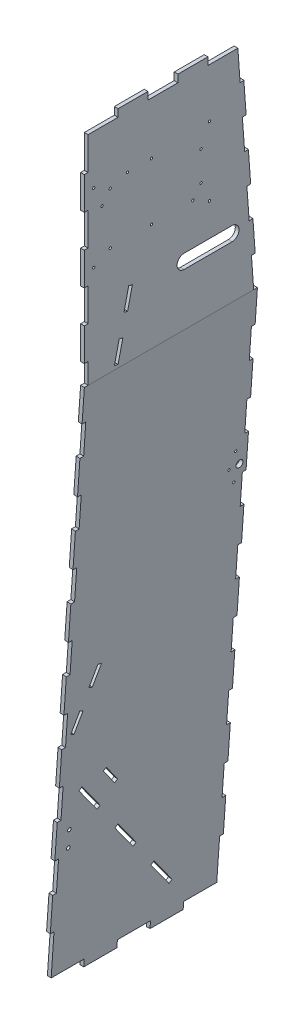
SolidWorks part; units mm, degrees
material "A-Glass Fiber"
ref_plane "Front Plane" through (0, 0, 0) normal (0, 0, 1) x (1, 0, 0)
ref_plane "Top Plane" through (0, 0, 0) normal (0, 1, 0) x (1, 0, 0)
ref_plane "Right Plane" through (0, 0, 0) normal (1, 0, 0) x (0, 0, -1)
sketch "Sketch1" plane through (0, 0, 0) normal (0, 0, 1) x (1, 0, 0)
  line L0 (-215.8818, 2052.32) -> (-215.8818, 1463.04)
  line L1 (-215.8818, 1463.04) -> (-316.0886, 20.32)
  line L2 (-316.0886, 20.32) -> (-317.5, 0)
  line L4 (-215.8818, 2052.32) -> (-215.8818, 2072.64)
  line L6 (-215.8818, 2072.64) -> (-205.7153, 2072.64)
  line L7 (-205.7153, 2072.64) -> (-205.7153, 1463.04)
  line L8 (-205.7153, 1463.04) -> (-307.3335, 0)
  line L9 (-317.5, 0) -> (-307.3335, 0)
  line L10 (-371.5407, 0) -> (-280.9748, 0) construction
  line L13 (-371.5407, 20.32) -> (-280.9748, 20.32) construction
  line L15 (-205.7153, 1463.04) -> (205.7153, 1463.04) construction
  point P23 (-305.9221, 20.32)
  dimension "D1" = 307.3335
extrude "Boss-Extrude1" add sketch "Sketch1" against normal blind 469.9
sketch "Sketch2" plane through (-315.9757, 21.9467, 0) normal (-0.9976, 0.0693, 0) x (0, 0, 1)
  line L35 (0, 1355.6785) -> (0, 0.1049)
  line L37 (-234.95, 1444.5652) -> (-234.95, -21.9996) construction
  line L40 (-10.16, 0.1049) -> (0, 0.1049)
  line L43 (-10.16, 0.1049) -> (-10.16, -21.9996)
  line L46 (0, 1272.0274) -> (-10.16, 1272.0274)
  line L47 (-10.16, 1355.6785) -> (-10.16, 1272.0274)
  line L48 (0, 1355.6785) -> (-10.16, 1355.6785)
  line L49 (0, 1177.9051) -> (-10.16, 1177.9051)
  line L50 (-10.16, 1177.9051) -> (-10.16, 1094.2274)
  line L51 (0, 1094.2274) -> (-10.16, 1094.2274)
  line L52 (0, 916.4274) -> (-10.16, 916.4274)
  line L53 (-10.16, 1000.1317) -> (-10.16, 916.4274)
  line L54 (0, 1000.1317) -> (-10.16, 1000.1317)
  line L55 (0, 822.3583) -> (-10.16, 822.3583)
  line L56 (0, 738.6274) -> (-10.16, 738.6274)
  line L57 (-10.16, 822.3583) -> (-10.16, 738.6274)
  line L58 (0, 644.5849) -> (-10.16, 644.5849)
  line L59 (-10.16, 644.5849) -> (-10.16, 560.8274)
  line L60 (0, 560.8274) -> (-10.16, 560.8274)
  line L61 (0, 466.8115) -> (-10.16, 466.8115)
  line L62 (-10.16, 466.8115) -> (-10.16, 383.0274)
  line L63 (0, 383.0274) -> (-10.16, 383.0274)
  line L64 (0, 289.0381) -> (-10.16, 289.0381)
  line L65 (-10.16, 289.0381) -> (-10.16, 205.2274)
  line L66 (0, 205.2274) -> (-10.16, 205.2274)
  line L67 (0, 111.2647) -> (-10.16, 111.2647)
  line L68 (-10.16, 111.2647) -> (-10.16, 0.1049)
  line L69 (0, 0.1049) -> (-10.16, 0.1049)
  line L70 (-10.16, -21.9996) -> (0, -21.9996)
  line L71 (0, 0.1049) -> (0, -21.9996)
  line L72 (-469.9, 1444.5652) -> (0, 1444.5652) construction
  line L73 (-469.9, -21.9996) -> (0, -21.9996) construction
  line L74 (-469.9, 0.1049) -> (-469.9, -21.9996)
  line L75 (-459.74, -21.9996) -> (-469.9, -21.9996)
  line L76 (-469.9, 0.1049) -> (-459.74, 0.1049)
  line L77 (-459.74, 111.2647) -> (-459.74, 0.1049)
  line L78 (-469.9, 111.2647) -> (-459.74, 111.2647)
  line L79 (-469.9, 205.2274) -> (-459.74, 205.2274)
  line L80 (-459.74, 289.0381) -> (-459.74, 205.2274)
  line L81 (-469.9, 289.0381) -> (-459.74, 289.0381)
  line L82 (-469.9, 383.0274) -> (-459.74, 383.0274)
  line L83 (-459.74, 466.8115) -> (-459.74, 383.0274)
  line L84 (-469.9, 466.8115) -> (-459.74, 466.8115)
  line L85 (-469.9, 560.8274) -> (-459.74, 560.8274)
  line L86 (-459.74, 644.5849) -> (-459.74, 560.8274)
  line L87 (-469.9, 644.5849) -> (-459.74, 644.5849)
  line L88 (-459.74, 822.3583) -> (-459.74, 738.6274)
  line L89 (-469.9, 738.6274) -> (-459.74, 738.6274)
  line L90 (-469.9, 822.3583) -> (-459.74, 822.3583)
  line L91 (-469.9, 1000.1317) -> (-459.74, 1000.1317)
  line L92 (-459.74, 1000.1317) -> (-459.74, 916.4274)
  line L93 (-469.9, 916.4274) -> (-459.74, 916.4274)
  line L94 (-469.9, 1094.2274) -> (-459.74, 1094.2274)
  line L95 (-459.74, 1177.9051) -> (-459.74, 1094.2274)
  line L96 (-469.9, 1177.9051) -> (-459.74, 1177.9051)
  line L97 (-469.9, 1355.6785) -> (-459.74, 1355.6785)
  line L98 (-459.74, 1355.6785) -> (-459.74, 1272.0274)
  line L99 (-469.9, 1272.0274) -> (-459.74, 1272.0274)
  line L100 (-459.74, 0.1049) -> (-459.74, -21.9996)
  line L101 (-459.74, 0.1049) -> (-469.9, 0.1049)
  line L102 (-469.9, 1355.6785) -> (-469.9, 0.1049)
  line L103 (-469.9, 1444.5652) -> (-469.9, -21.9996) construction
  line L104 (-459.74, 205.2274) -> (-469.9, 205.2274) construction
  line M1 (0, -21.9996) -> (0, 1444.5652)
  line M3 (-469.9, 1444.5652) -> (-469.9, -21.9996)
  line M4 (-469.9, -21.9996) -> (0, -21.9996)
extrude "Cut-Extrude1" cut sketch "Sketch2" against normal blind 10.16 contours L66 L35 L64 L65 | L69 L67 L68 M1 | L60 L35 L58 L59 | L63 L35 L61 L62 | L55 L57 L56 L35 | L35 L54 L53 L52 | L51 L35 L49 L50 | L35 L48 L47 L46 | L40 L43 M4 M1 | L100 L76 M3 M4 | L78 L76 L77 M3 | L81 L79 L80 M3 | L84 L82 L83 M3 | L87 L85 L86 M3 | L90 L89 L88 M3 | L93 L92 L91 M3 | L96 L94 L95 M3 | L99 L98 L97 M3 region at (-224.9388, 1332.6419, -464.82) region at (-237.2577, 1155.2825, -464.82) region at (-249.5765, 977.9231, -464.82) region at (-261.8953, 800.5637, -464.82) region at (-274.2142, 623.2043, -464.82) region at (-286.533, 445.8449, -464.82) region at (-298.8518, 268.4855, -464.82) region at (-316.7342, 11.0257, -464.82) region at (-312.1173, 77.4977, -5.08) region at (-298.8518, 268.4855, -5.08) region at (-286.533, 445.8449, -5.08) region at (-274.2142, 623.2043, -5.08) region at (-261.8953, 800.5637, -5.08) region at (-249.5765, 977.9231, -5.08) region at (-237.2577, 1155.2825, -5.08) region at (-224.9388, 1332.6419, -5.08) region at (-316.7342, 11.0257, -5.08) region at (-312.1173, 77.4977, -464.82)
sketch "Sketch3" plane through (-215.8818, 0, 0) normal (-1, 0, 0) x (0, 0, 1)
  line L0 (0, 2052.32) -> (-10.16, 2052.32) construction
  line L1 (0, 1963.42) -> (-10.16, 1963.42) construction
  line L2 (-10.16, 2052.32) -> (-10.16, 1963.42) construction
  line L3 (0, 1874.52) -> (-10.16, 1874.52) construction
  line L4 (0, 1463.04) -> (0, 2072.64)
  line L5 (0, 2072.64) -> (-469.9, 2072.64)
  line L6 (-469.9, 2072.64) -> (-469.9, 1463.04)
  line L8 (0, 1463.04) -> (0, 2072.64)
  line L9 (0, 2072.64) -> (-469.9, 2072.64)
  line L12 (0, 1785.62) -> (-10.16, 1785.62) construction
  line L13 (-10.16, 1874.52) -> (-10.16, 1785.62) construction
  line L14 (0, 1696.72) -> (-10.16, 1696.72) construction
  line L15 (0, 1607.82) -> (-10.16, 1607.82) construction
  line L16 (-10.16, 1696.72) -> (-10.16, 1607.82) construction
  line L17 (0, 1518.92) -> (-10.16, 1518.92) construction
  line L18 (-10.16, 1518.92) -> (-10.16, 1488.44) construction
  line L19 (0, 2052.32) -> (-10.16, 2052.32)
  line L20 (0, 1963.42) -> (-10.16, 1963.42)
  line L21 (-10.16, 2052.32) -> (-10.16, 1963.42)
  line L22 (0, 1874.52) -> (-10.16, 1874.52)
  line L23 (0, 1785.62) -> (-10.16, 1785.62)
  line L24 (-10.16, 1874.52) -> (-10.16, 1785.62)
  line L25 (0, 1696.72) -> (-10.16, 1696.72)
  line L26 (0, 1607.82) -> (-10.16, 1607.82)
  line L27 (-10.16, 1696.72) -> (-10.16, 1607.82)
  line L28 (0, 1518.92) -> (-10.16, 1518.92)
  line L29 (-10.16, 1518.92) -> (-10.16, 1488.44)
  line L30 (0, 2052.32) -> (0, 1463.04)
  line L31 (-234.95, 1463.04) -> (-234.95, 2072.64) construction
  line L32 (-10.16, 2052.32) -> (0, 2052.32)
  line L33 (-10.16, 2052.32) -> (-10.16, 2072.64)
  line L34 (-10.16, 2072.64) -> (0, 2072.64)
  line L35 (0, 2052.32) -> (0, 2072.64)
  line L36 (-469.9, 1463.04) -> (-425.45, 2072.64)
  line L37 (-469.9, 1463.04) -> (-463.754, 1547.3284)
  line L38 (-469.9, 1463.04) -> (-459.7669, 1462.3011)
  line L39 (-463.754, 1547.3284) -> (-453.6209, 1546.5895)
  line L40 (-459.7669, 1462.3011) -> (-453.6209, 1546.5895)
  line L41 (-463.754, 1547.3284) -> (-453.6209, 1546.5895)
  line L42 (-463.754, 1547.3284) -> (-457.6079, 1631.6168)
  line L43 (-453.6209, 1546.5895) -> (-447.4748, 1630.8779)
  line L44 (-457.6079, 1631.6168) -> (-447.4748, 1630.8779)
  line L45 (-457.6079, 1631.6168) -> (-447.4748, 1630.8779)
  line L46 (-457.6079, 1631.6168) -> (-451.4619, 1715.9052)
  line L47 (-447.4748, 1630.8779) -> (-441.3288, 1715.1664)
  line L48 (-451.4619, 1715.9052) -> (-441.3288, 1715.1664)
  line L49 (-451.4619, 1715.9052) -> (-441.3288, 1715.1664)
  line L50 (-451.4619, 1715.9052) -> (-445.3159, 1800.1936)
  line L51 (-441.3288, 1715.1664) -> (-435.1828, 1799.4548)
  line L52 (-445.3159, 1800.1936) -> (-435.1828, 1799.4548)
  line L53 (-445.3159, 1800.1936) -> (-435.1828, 1799.4548)
  line L54 (-10.16, 1488.44) -> (-10.16, 1463.04)
  line L56 (-445.3159, 1800.1936) -> (-439.1699, 1884.4821)
  line L57 (-435.1828, 1799.4548) -> (-429.0368, 1883.7432)
  line L58 (-439.1699, 1884.4821) -> (-429.0368, 1883.7432)
  line L59 (-439.1699, 1884.4821) -> (-429.0368, 1883.7432)
  line L60 (-439.1699, 1884.4821) -> (-433.0238, 1968.7705)
  line L61 (-429.0368, 1883.7432) -> (-422.8907, 1968.0316)
  line L62 (-433.0238, 1968.7705) -> (-422.8907, 1968.0316)
  line L63 (-10.16, 2052.32) -> (-469.9, 2052.32) construction
  line L64 (-469.9, 2072.64) -> (-469.9, 1463.04) construction
  line L65 (-433.0238, 1968.7705) -> (-422.8907, 1968.0316)
  line L66 (-433.0238, 1968.7705) -> (-426.8778, 2053.0589)
  line L67 (-422.8907, 1968.0316) -> (-416.7447, 2052.32)
  line L68 (-426.8778, 2053.0589) -> (-416.7447, 2052.32)
  line L69 (-416.7447, 2052.32) -> (-426.9317, 2052.32)
  line L70 (-426.8778, 2053.0589) -> (-416.7447, 2052.32)
  line L71 (-426.8778, 2053.0589) -> (-425.3531, 2073.9694)
  line L72 (-416.7447, 2052.32) -> (-415.22, 2073.2306)
  line L73 (-425.3531, 2073.9694) -> (-415.22, 2073.2306)
  line L74 (-469.9, 1463.04) -> (0, 1463.04) construction
  line L78 (-469.9, 1463.04) -> (0, 1463.04)
  line L79 (-469.9, 1463.04) -> (0, 1463.04)
  line M7 (0, 1463.04) -> (0, 2072.64)
  line M8 (0, 2072.64) -> (-469.9, 2072.64)
  line M9 (-469.9, 2072.64) -> (-469.9, 1463.04)
  line M10 (-469.9, 1463.04) -> (0, 1463.04)
  dimension "D2" = 44.45
  dimension "D3" = 10.16
  dimension "D1" = 0
extrude "Cut-Extrude2" cut sketch "Sketch3" against normal blind 12.7 contours M10 | L29 L54 L28 M10 M7 | L36 L66 M9 M8 | L48 L36 L44 L47 | L58 L36 L52 L57 | L67 L69 L36 L62 | L25 L27 L26 L8 | L22 L24 L23 L8 | L19 L21 L20 L8 | L33 L19 L8 M8 | L68 L72 L36 M8 | L69 L68 L66 region at (-215.8818, 1490.98, -5.08) region at (-215.8818, 1652.27, -5.08) region at (-215.8818, 1504.9998, -461.7544) region at (-215.8818, 1869.44, -455.0833) region at (-215.8818, 1830.07, -5.08) region at (-215.8818, 1673.3916, -449.4684) region at (-215.8818, 2062.6636, -421.0525) region at (-215.8818, 2007.87, -5.08) region at (-215.8818, 1841.9684, -437.1763) region at (-215.8818, 2052.5663, -423.5181) region at (-215.8818, 2062.48, -5.08) region at (-215.8818, 2010.3602, -424.8903)
sketch "Sketch4" plane through (-215.8818, 0, 0) normal (-1, 0, 0) x (0, 0, 1)
  line L1 (-416.7447, 2072.64) -> (-335.4278, 2072.64)
  line L2 (-416.7447, 2072.64) -> (-416.7447, 2052.32)
  line L3 (-416.7447, 2052.32) -> (-335.4278, 2052.32)
  line L4 (-335.4278, 2072.64) -> (-335.4278, 2052.32)
  line L5 (-10.16, 2072.64) -> (-10.16, 1963.42) construction
  line L6 (-335.4278, 2072.64) -> (-254.1108, 2072.64)
  line L7 (-335.4278, 2072.64) -> (-335.4278, 2052.32)
  line L8 (-335.4278, 2052.32) -> (-254.1108, 2052.32)
  line L9 (-254.1108, 2072.64) -> (-254.1108, 2052.32)
  line L10 (-254.1108, 2072.64) -> (-172.7939, 2072.64)
  line L11 (-254.1108, 2072.64) -> (-254.1108, 2052.32)
  line L12 (-254.1108, 2052.32) -> (-172.7939, 2052.32)
  line L13 (-172.7939, 2072.64) -> (-172.7939, 2052.32)
  line L14 (-172.7939, 2072.64) -> (-91.4769, 2072.64)
  line L15 (-172.7939, 2072.64) -> (-172.7939, 2052.32)
  line L16 (-172.7939, 2052.32) -> (-91.4769, 2052.32)
  line L17 (-91.4769, 2072.64) -> (-91.4769, 2052.32)
  line L18 (-91.4769, 2072.64) -> (-10.16, 2072.64)
  line L19 (-91.4769, 2072.64) -> (-91.4769, 2052.32)
  line L20 (-91.4769, 2052.32) -> (-10.16, 2052.32)
  line L21 (-10.16, 2072.64) -> (-10.16, 2052.32)
  line L23 (-422.8907, 1968.0316) -> (-415.263, 2072.64) construction
  line L24 (-415.263, 2072.64) -> (-10.16, 2072.64) construction
  line M26 (-10.16, 1963.42) -> (-10.16, 2072.64)
  line M27 (-10.16, 2072.64) -> (-415.263, 2072.64)
  dimension "D1" = 20.32
extrude "Cut-Extrude3" cut sketch "Sketch4" against normal blind 12.7 contours L4 L3 M27 | L13 L9 L12 M27 | L17 L20 M26 M27 region at (-215.8818, 2062.48, -376.0862) region at (-215.8818, 2062.48, -213.4523) region at (-215.8818, 2062.48, -50.8185)
sketch "Sketch5" plane through (-315.9757, 21.9467, 0) normal (-0.9976, 0.0693, 0) x (0, 0, 1)
  line L1 (-459.74, -21.9996) -> (-369.824, -21.9996)
  line L2 (-459.74, -21.9996) -> (-459.74, -1.6796)
  line L3 (-459.74, -1.6796) -> (-369.824, -1.6796)
  line L4 (-369.824, -21.9996) -> (-369.824, -1.6796)
  line L5 (-369.824, -21.9996) -> (-279.908, -21.9996)
  line L6 (-369.824, -21.9996) -> (-369.824, -1.6796)
  line L7 (-369.824, -1.6796) -> (-279.908, -1.6796)
  line L8 (-279.908, -21.9996) -> (-279.908, -1.6796)
  line L9 (-279.908, -21.9996) -> (-189.992, -21.9996)
  line L10 (-279.908, -21.9996) -> (-279.908, -1.6796)
  line L11 (-279.908, -1.6796) -> (-189.992, -1.6796)
  line L12 (-189.992, -21.9996) -> (-189.992, -1.6796)
  line L13 (-189.992, -21.9996) -> (-100.076, -21.9996)
  line L14 (-189.992, -21.9996) -> (-189.992, -1.6796)
  line L15 (-189.992, -1.6796) -> (-100.076, -1.6796)
  line L16 (-100.076, -21.9996) -> (-100.076, -1.6796)
  line L17 (-100.076, -21.9996) -> (-10.16, -21.9996)
  line L18 (-100.076, -21.9996) -> (-100.076, -1.6796)
  line L19 (-100.076, -1.6796) -> (-10.16, -1.6796)
  line L20 (-10.16, -21.9996) -> (-10.16, -1.6796)
  line L21 (-10.16, 111.2647) -> (-10.16, -21.9996) construction
  dimension "D1" = 20.32
extrude "Cut-Extrude4" cut sketch "Sketch5" against normal blind 12.7 contours L1 L4 L3 L2 | L9 L12 L11 L8 | L17 L20 L19 L18 L16 region at (-316.796, 10.1356, -414.782) region at (-316.796, 10.1356, -234.95) region at (-316.796, 10.1356, -55.118)
sketch "Sketch6" plane through (-315.9757, 21.9467, 0) normal (-0.9976, 0.0693, 0) x (0, 0, 1)
  line L0 (-217.3726, 211.9965) -> (-163.4402, 285.2141)
  line L1 (-325.2304, 65.5562) -> (-271.298, 138.7738)
  line L2 (-44.1085, 632.6765) -> (-22.5289, 586.4358) construction
  line L3 (-74.8989, 674.6188) -> (-65.6881, 678.9173) construction
  line L8 (-271.6486, 139.032) -> (-279.8219, 145.0526) construction
  line L56 (-87.2678, 725.158) -> (-65.6881, 678.9173) construction
  line L57 (-74.8989, 674.6188) -> (-96.4785, 720.8595) construction
  line L58 (-31.7396, 582.1373) -> (-22.5289, 586.4358) construction
  line L59 (-31.7396, 582.1373) -> (-53.3192, 628.3781) construction
  line L60 (-53.3192, 628.3781) -> (-44.1085, 632.6765) construction
  line L63 (-117.6881, 364.4573) -> (-63.7557, 437.6749) construction
  line L65 (-225.5528, 218.0222) -> (-171.6205, 291.2397) construction
  line L69 (-333.4176, 71.587) -> (-279.4852, 144.8046) construction
  line L70 (-109.5008, 358.4266) -> (-55.5685, 431.6442)
  line L71 (-44.1085, 632.6765) -> (-22.5289, 586.4358)
  line L72 (-74.8989, 674.6188) -> (-65.6881, 678.9173)
  line L73 (-87.2678, 725.158) -> (-65.6881, 678.9173)
  line L74 (-74.8989, 674.6188) -> (-96.4785, 720.8595)
  line L75 (-31.7396, 582.1373) -> (-22.5289, 586.4358)
  line L76 (-31.7396, 582.1373) -> (-53.3192, 628.3781)
  line L77 (-53.3192, 628.3781) -> (-44.1085, 632.6765)
  line L78 (-109.5008, 358.4266) -> (-117.6881, 364.4573)
  line L79 (-55.5685, 431.6442) -> (-63.7557, 437.6749)
  line L80 (-117.6881, 364.4573) -> (-63.7557, 437.6749)
  line L81 (-163.4402, 285.2141) -> (-171.6205, 291.2397)
  line L82 (-225.5528, 218.0222) -> (-171.6205, 291.2397)
  line L83 (-217.3726, 211.9965) -> (-225.5528, 218.0222)
  line L84 (-271.298, 138.7738) -> (-279.4852, 144.8046)
  line L85 (-325.2304, 65.5562) -> (-333.4176, 71.587)
  line L86 (-333.4176, 71.587) -> (-279.4852, 144.8046)
  line L87 (-87.2678, 725.158) -> (-96.4785, 720.8595)
  line L89 (-109.8514, 358.6848) -> (-118.0248, 364.7053) construction
  line L90 (-163.7838, 285.4672) -> (-171.9572, 291.4877) construction
  line L91 (-217.7162, 212.2496) -> (-225.8895, 218.2702) construction
  dimension "D1" = 10.16
extrude "Cut-Extrude5" cut sketch "Sketch6" against normal blind 137.414 contours L73 L87 L74 L72 | L77 L76 L75 L71 | L80 L78 | L83 L81 L82 | L86 L85 L84 region at (-298.541, 272.9601, -194.4965) region at (-308.6877, 126.8743, -302.3578) region at (-288.3947, 419.0407, -86.6283) region at (-273.8885, 627.8938, -37.9241) region at (-267.4804, 720.1529, -81.0833)
sketch "Sketch8" plane through (-215.8818, 0, 0) normal (-1, 0, 0) x (0, 0, 1)
  circle A0 centre (-450.215, 1043.94) radius 9.525 construction
  circle A1 centre (-450.215, 1043.94) radius 9.525
extrude "Cut-Extrude7" cut sketch "Sketch8" along normal through all
sketch "Sketch13" plane through (-215.8818, 0, 0) normal (-1, 0, 0) x (0, 0, 1)
  line L0 (-413.556, 1633.6344) -> (-413.556, 1614.5844)
  line L1 (-270.8715, 1611.4094) -> (-270.8715, 1636.8094)
  line L2 (-413.556, 1624.1094) -> (-270.8715, 1624.1094) construction
  line L3 (-270.8715, 1624.1094) -> (-400.856, 1624.1094) construction
  line L4 (-270.8715, 1605.0594) -> (-400.856, 1605.0594)
  line L5 (-270.8715, 1643.1594) -> (-400.856, 1643.1594)
  line L6 (-416.7447, 2052.32) -> (-335.4278, 2052.32)
  line L7 (-422.8907, 1968.0316) -> (-416.7447, 2052.32)
  circle A0 centre (-25.2465, 1731.87) radius 3.175
  circle A1 centre (-70.409, 1755.42) radius 3.175
  circle A2 centre (-182.409, 1755.42) radius 3.175
  circle A3 centre (-25.2465, 1918.97) radius 3.175
  circle A4 centre (-47.789, 1865.42) radius 3.175
  circle A5 centre (-182.409, 1910.42) radius 3.175
  circle A6 centre (-117.079, 1910.42) radius 3.175
  circle A7 centre (-70.409, 1895.42) radius 3.175
  circle A8 centre (-317.029, 1865.42) radius 3.175
  circle A9 centre (-294.409, 1755.42) radius 3.175
  circle A10 centre (-317.029, 1785.42) radius 3.175
  circle A11 centre (-339.5715, 1731.87) radius 3.175
  circle A12 centre (-339.5715, 1918.97) radius 3.175
  arc A13 (-270.8715, 1605.0594) -> (-270.8715, 1643.1594) centre (-270.8715, 1624.1094) ccw
  arc A14 (-400.856, 1643.1594) -> (-400.856, 1605.0594) centre (-400.856, 1624.1094) ccw
  point P34 (-335.8637, 1624.1094)
  point P42 (-416.7447, 2052.32)
  dimension "D1" = 12.7
  dimension "D2" = 19.05
extrude "Cut-Extrude8" cut sketch "Sketch13" against normal through all contours L5 A14 L4 A13 | A11 | A10 | A9 | A2 | A1 | A0 | A4 | A7 | A6 | A3 | A5 | A8 | A12 | L0 A14 region at (-215.8818, 1624.1094, -335.8637) region at (-215.8818, 1731.87, -25.2465) region at (-215.8818, 1755.42, -70.409) region at (-215.8818, 1755.42, -182.409) region at (-215.8818, 1918.97, -25.2465) region at (-215.8818, 1865.42, -47.789) region at (-215.8818, 1910.42, -182.409) region at (-215.8818, 1910.42, -117.079) region at (-215.8818, 1895.42, -70.409) region at (-215.8818, 1865.42, -317.029) region at (-215.8818, 1755.42, -294.409) region at (-215.8818, 1785.42, -317.029) region at (-215.8818, 1731.87, -339.5715) region at (-215.8818, 1918.97, -339.5715)
sketch "Sketch17" plane through (-215.8818, 0, 0) normal (-1, 0, 0) x (0, 0, 1)
  line L0 (-130.4243, 1639.6605) -> (-120.5247, 1641.946)
  line L1 (-120.5247, 1641.946) -> (-107.584, 1585.8939)
  line L2 (-130.4243, 1639.6605) -> (-117.4836, 1583.6084)
  line L3 (-117.4836, 1583.6084) -> (-107.584, 1585.8939)
  line L4 (-104.543, 1527.5563) -> (-94.6434, 1529.8418)
  line L5 (-91.6023, 1471.5043) -> (-104.543, 1527.5563)
  line L6 (-91.6023, 1471.5043) -> (-81.7027, 1473.7898)
  line L7 (-81.7027, 1473.7898) -> (-94.6434, 1529.8418)
  line L8 (-416.7447, 2052.32) -> (-335.4278, 2052.32)
  line L9 (-422.8907, 1968.0316) -> (-416.7447, 2052.32)
  point P11 (-416.7447, 2052.32)
extrude "Cut-Extrude9" cut sketch "Sketch17" against normal through all contours L6 L7 L4 L5 | L2 L3 L1 L0 region at (-215.8818, 1612.7772, -119.0041) region at (-215.8818, 1500.6731, -93.1229)
sketch "Sketch20" plane through (-315.9757, 21.9467, 0) normal (-0.9976, 0.0693, 0) x (0, 0, 1)
  line L0 (-441.6805, 375.8656) -> (-258.1103, 563.7707)
  line L1 (-258.1103, 563.7707) -> (-341.7803, 797.9819)
  line L2 (-258.1103, 563.7707) -> (-10.16, 315.8204)
  line L3 (-258.1103, 563.7707) -> (-258.6478, 797.9819)
  line L8 (-10.16, 110.1771) -> (-10.16, -1.6796)
  line L9 (-10.16, 466.8115) -> (-10.16, 383.0274) construction
  line L10 (-13.335, 290.1376) -> (-13.335, 359.9876)
  line L11 (-13.335, 290.1376) -> (-48.26, 290.1376)
  line L12 (-13.335, 359.9876) -> (-48.26, 359.9876)
  line L13 (-48.26, 290.1376) -> (-48.26, 359.9876)
  line L32 (-120.9293, 445.7124) -> (-154.8235, 399.6982)
  line L33 (-120.9293, 445.7124) -> (-128.5983, 451.3614)
  line L34 (-154.8235, 399.6982) -> (-162.4926, 405.3473)
  line L35 (-128.5983, 451.3614) -> (-162.4926, 405.3473)
  line L37 (-109.5008, 358.4266) -> (-117.6881, 364.4573) construction
  line L38 (-117.6881, 364.4573) -> (-63.7557, 437.6749) construction
  line L39 (-137.8764, 422.7053) -> (43.6586, 288.9858) construction
  line L40 (-35.56, 332.8883) -> (-35.56, 361.687) construction
  line L41 (-10.16, 466.8115) -> (-10.16, 383.0274)
  circle A0 centre (-35.56, 347.2876) radius 4.7625
  circle A2 centre (-35.56, 302.8376) radius 4.7625
  point P11 (-10.16, -1.6796)
  point P57 (-35.56, 341.2204)
  dimension "D9" = 44.45
  dimension "D15" = 9.525
  dimension "D3" = 3.175
  dimension "D4" = 12.7
  dimension "D5" = 57.15
  dimension "D6" = 317.5
  dimension "D7" = 12.7
  dimension "D8" = 12.7
  dimension "D22" = 9.525
  dimension "D23" = 6.35
  dimension "D24" = 50.8
  dimension "D25" = 34.925
extrude "Cut-Extrude10" cut sketch "Sketch20" against normal through all contours A2 | L2 A0 | L2 A0 | L2 L35 L34 L32 | L33 L35 L2 L32 region at (-285.2619, 464.1454, -128.5379) region at (-286.8509, 441.2683, -145.572) region at (-291.908, 368.4591, -35.5004) region at (-292.1316, 365.2395, -38.7278) region at (-294.992, 324.0565, -35.56)
sketch "Sketch22" [suppressed] plane through (-315.9757, 21.9467, 0) normal (-0.9976, 0.0693, 0) x (0, 0, 1)
  line L3 (-138.6114, 421.183) -> (-138.6114, 431.343)
  line L4 (-138.6114, 431.343) -> (-202.8371, 431.343)
  line L5 (-138.6114, 421.183) -> (-202.8371, 421.183)
  line L6 (-202.8371, 421.183) -> (-202.8371, 431.343)
  line L7 (-267.0629, 421.183) -> (-267.0629, 431.343)
  line L8 (-267.0629, 431.343) -> (-331.2886, 431.343)
  line L9 (-267.0629, 421.183) -> (-331.2886, 421.183)
  line L10 (-331.2886, 421.183) -> (-331.2886, 431.343)
  line L11 (-395.5143, 421.183) -> (-395.5143, 431.343)
  line L12 (-395.5143, 421.183) -> (-459.74, 421.183)
  line L13 (-395.5143, 431.343) -> (-459.74, 431.343)
  line L15 (-459.74, 421.183) -> (-459.74, 431.343)
  line L16 (-100.076, -1.6796) -> (-10.16, -1.6796) construction
  line L17 (-10.16, 111.2647) -> (-10.16, -1.6796) construction
  line L18 (-100.076, -1.6796) -> (-10.16, -1.6796)
  line L19 (-10.16, 111.2647) -> (-10.16, -1.6796)
  point P0 (-10.16, -1.6796)
sketch "Sketch23" plane through (-315.9757, 21.9467, 0) normal (-0.9976, 0.0693, 0) x (0, 0, 1)
  line L2 (-450.215, 1024.4555) -> (-396.5689, 1024.4555) construction
  line L3 (-437.515, 986.3555) -> (-437.515, 1062.5555) construction
  circle A0 centre (-437.515, 986.3555) radius 3.175
  circle A1 centre (-421.64, 1024.4555) radius 3.175
  circle A2 centre (-437.515, 1062.5555) radius 3.175
  point P21 (-437.515, 1024.4555)
  dimension "D1" = 6.35
  dimension "D2" = 28.575
  dimension "D3" = 76.2
  dimension "D4" = 12.7
extrude "Cut-Extrude11" cut sketch "Sketch23" against normal through all contours A1 | A0 | A2 region at (-247.6311, 1005.9316, -437.515) region at (-244.9912, 1043.94, -421.64) region at (-242.3512, 1081.9484, -437.515)
